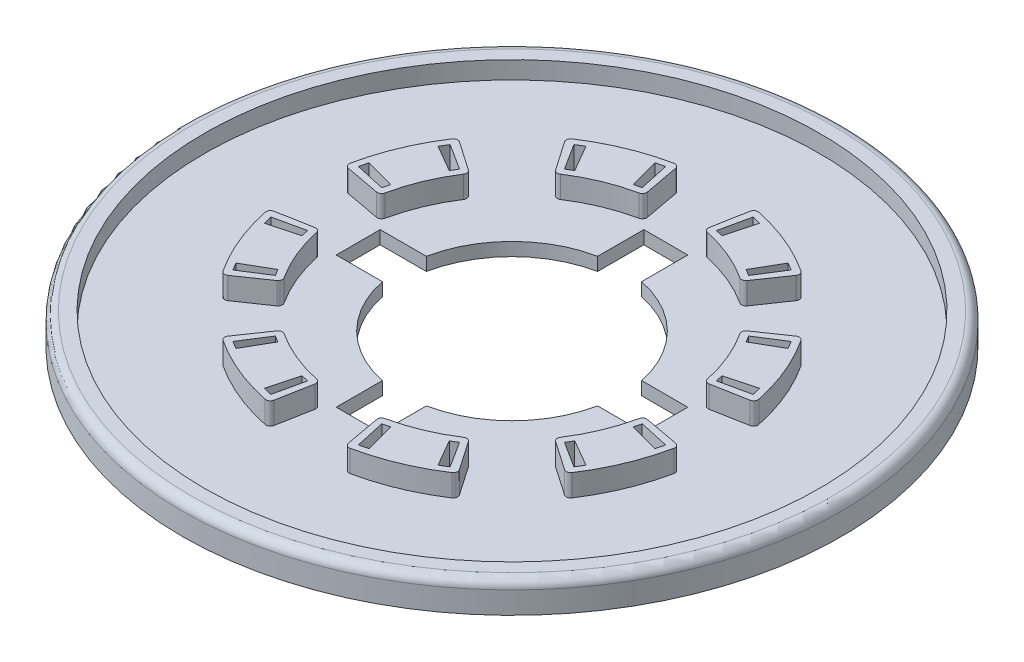
SolidWorks part; units mm, degrees
ref_plane "Alzado" through (0, 0, 0) normal (0, 0, 1) x (1, 0, 0)
ref_plane "Planta" through (0, 0, 0) normal (0, 1, 0) x (1, 0, 0)
ref_plane "Vista lateral" through (0, 0, 0) normal (1, 0, 0) x (0, 0, -1)
sketch "Croquis1" plane through (0, 0, 0) normal (0, 1, 0) x (1, 0, 0)
  circle A0 centre (0, 0) radius 75
  dimension "D1" = 150
extrude "Saliente-Extruir1" add sketch "Croquis1" along normal blind 3
sketch "Croquis3" plane through (0, 3, 0) normal (0, 1, 0) x (1, 0, 0)
  line L0 (-70, 0) -> (70, 0) construction
  line L1 (0, -70) -> (0, 70) construction
  line L3 (-49.4975, -49.4975) -> (49.4975, 49.4975) construction
  line L5 (-49.4975, 49.4975) -> (49.4975, -49.4975) construction
  circle A0 centre (0, 0) radius 75
  circle A1 centre (0, 0) radius 70
  dimension "D1" = 150
  dimension "D2" = 5
extrude "Saliente-Extruir2" add sketch "Croquis3" along normal blind 4
sketch "Croquis7" plane through (0, 3, 0) normal (0, 1, 0) x (1, 0, 0)
  line L0 (51.6188, -52.6795) -> (52.6795, -51.6188)
  line L9 (73.75, -0.75) -> (-73.75, -0.75)
  line L10 (73.75, -0.75) -> (73.75, 0.75)
  line L11 (73.75, 0.75) -> (-73.75, 0.75)
  line L12 (-73.75, -0.75) -> (-73.75, 0.75)
  line L13 (73.75, -0.75) -> (-73.75, 0.75) construction
  line L14 (73.75, 0.75) -> (-73.75, -0.75) construction
  line L15 (51.6188, -52.6795) -> (-52.6795, 51.6188)
  line L16 (-52.6795, 51.6188) -> (-51.6188, 52.6795)
  line L17 (52.6795, -51.6188) -> (-51.6188, 52.6795)
  line L18 (-0.75, -73.75) -> (0.75, -73.75)
  line L19 (-0.75, -73.75) -> (-0.75, 73.75)
  line L20 (-0.75, 73.75) -> (0.75, 73.75)
  line L21 (0.75, -73.75) -> (0.75, 73.75)
  line L22 (-52.6795, -51.6188) -> (-51.6188, -52.6795)
  line L23 (-52.6795, -51.6188) -> (51.6188, 52.6795)
  line L24 (51.6188, 52.6795) -> (52.6795, 51.6188)
  line L25 (-51.6188, -52.6795) -> (52.6795, 51.6188)
  line L26 (-73.75, 0.75) -> (-73.75, -0.75)
  line L27 (-73.75, 0.75) -> (73.75, 0.75)
  line L28 (73.75, 0.75) -> (73.75, -0.75)
  line L29 (-73.75, -0.75) -> (73.75, -0.75)
  point P0 (0, 0)
  point P25 (0, 0)
  dimension "D1" = 1.5
  dimension "D2" = 147.5
  dimension "D3" = 5
sketch "Croquis2" plane through (0, 0, 0) normal (0, -1, 0) x (1, 0, 0)
  line L0 (0, 0) -> (-75, 0) construction
  line L2 (0, 0) -> (-69.291, 28.7013) construction
  circle A0 centre (0, 0) radius 75 construction
  circle A1 centre (-55.4328, 22.961) radius 3.75
  circle A2 centre (-22.961, 55.4328) radius 3.75
  circle A3 centre (22.961, 55.4328) radius 3.75
  circle A4 centre (55.4328, 22.961) radius 3.75
  circle A5 centre (55.4328, -22.961) radius 3.75
  circle A6 centre (22.961, -55.4328) radius 3.75
  circle A7 centre (-22.961, -55.4328) radius 3.75
  circle A8 centre (-55.4328, -22.961) radius 3.75
  point P25 (0, 0)
  dimension "D1" = 7.5
  dimension "D2" = 60
  dimension "D4" = 22.5
  dimension "D3" = 8
extrude "Saliente-Extruir3" [suppressed] add sketch "Croquis7" along normal blind 1 contours L11 L19 L17 L15 | L11 L12 L9 L10 | L21 L20 L19 L18 | L23 L24 L25 L22 | L15 L16 L17 L0
sketch "Croquis4" plane through (0, 0, 0) normal (0, -1, 0) x (1, 0, 0)
  circle A0 centre (0, 0) radius 25
  dimension "D1" = 50
extrude "Cortar-Extruir2" cut sketch "Croquis4" against normal blind 6
sketch "Croquis8" plane through (0, 3, 0) normal (0, 1, 0) x (1, 0, 0)
  line L0 (-45.7108, -8.472) -> (-37.8425, -7.0137)
  line L1 (-38.313, -26.3318) -> (-31.7182, -21.7993)
  line L2 (-38.313, 26.3318) -> (-31.7182, 21.7993)
  line L4 (-45.7108, 8.472) -> (-37.8425, 7.0137)
  line L20 (0, 0) -> (-75, 0) construction
  line L35 (-8.472, 45.7108) -> (-7.0137, 37.8425)
  line L36 (-26.3318, 38.313) -> (-21.7993, 31.7182)
  line L37 (26.3318, 38.313) -> (21.7993, 31.7182)
  line L38 (8.472, 45.7108) -> (7.0137, 37.8425)
  line L39 (45.7108, 8.472) -> (37.8425, 7.0137)
  line L40 (38.313, 26.3318) -> (31.7182, 21.7993)
  line L41 (38.313, -26.3318) -> (31.7182, -21.7993)
  line L42 (45.7108, -8.472) -> (37.8425, -7.0137)
  line L43 (8.472, -45.7108) -> (7.0137, -37.8425)
  line L44 (26.3318, -38.313) -> (21.7993, -31.7182)
  line L45 (-26.3318, -38.313) -> (-21.7993, -31.7182)
  line L46 (-8.472, -45.7108) -> (-7.0137, -37.8425)
  circle A0 centre (0, 0) radius 37.5 construction
  circle A1 centre (0, 0) radius 47.5 construction
  arc A2 (-36.6821, -7.7892) -> (-31.446, -20.4303) centre (0, 0) ccw
  arc A3 (-39.7155, -26.0562) -> (-46.5077, -9.6586) centre (0, 0) cw
  circle A52 centre (0, 0) radius 75 construction
  arc A53 (-38.313, -26.3318) -> (-39.7155, -26.0562) centre (-38.8794, -25.5077) cw
  arc A54 (-31.7182, -21.7993) -> (-31.446, -20.4303) centre (-32.2846, -20.9752) ccw
  arc A55 (-37.8425, -7.0137) -> (-36.6821, -7.7892) centre (-37.6603, -7.997) cw
  arc A56 (-45.7108, -8.472) -> (-46.5077, -9.6586) centre (-45.5285, -9.4552) ccw
  arc A57 (-46.5077, 9.6586) -> (-39.7155, 26.0562) centre (0, 0) cw
  arc A58 (-38.313, 26.3318) -> (-39.7155, 26.0562) centre (-38.8794, 25.5077) ccw
  arc A59 (-45.7108, 8.472) -> (-46.5077, 9.6586) centre (-45.5285, 9.4552) cw
  arc A60 (-31.7182, 21.7993) -> (-31.446, 20.4303) centre (-32.2846, 20.9752) cw
  arc A61 (-31.446, 20.4303) -> (-36.6821, 7.7892) centre (0, 0) ccw
  arc A62 (-37.8425, 7.0137) -> (-36.6821, 7.7892) centre (-37.6603, 7.997) ccw
  arc A63 (-26.0562, 39.7155) -> (-9.6586, 46.5077) centre (0, 0) cw
  arc A64 (-8.472, 45.7108) -> (-9.6586, 46.5077) centre (-9.4552, 45.5285) ccw
  arc A65 (-26.3318, 38.313) -> (-26.0562, 39.7155) centre (-25.5077, 38.8794) cw
  arc A66 (-7.0137, 37.8425) -> (-7.7892, 36.6821) centre (-7.997, 37.6603) cw
  arc A67 (-7.7892, 36.6821) -> (-20.4303, 31.446) centre (0, 0) ccw
  arc A68 (-21.7993, 31.7182) -> (-20.4303, 31.446) centre (-20.9752, 32.2846) ccw
  arc A69 (9.6586, 46.5077) -> (26.0562, 39.7155) centre (0, 0) cw
  arc A70 (26.3318, 38.313) -> (26.0562, 39.7155) centre (25.5077, 38.8794) ccw
  arc A71 (8.472, 45.7108) -> (9.6586, 46.5077) centre (9.4552, 45.5285) cw
  arc A72 (21.7993, 31.7182) -> (20.4303, 31.446) centre (20.9752, 32.2846) cw
  arc A73 (20.4303, 31.446) -> (7.7892, 36.6821) centre (0, 0) ccw
  arc A74 (7.0137, 37.8425) -> (7.7892, 36.6821) centre (7.997, 37.6603) ccw
  arc A75 (39.7155, 26.0562) -> (46.5077, 9.6586) centre (0, 0) cw
  arc A76 (45.7108, 8.472) -> (46.5077, 9.6586) centre (45.5285, 9.4552) ccw
  arc A77 (38.313, 26.3318) -> (39.7155, 26.0562) centre (38.8794, 25.5077) cw
  arc A78 (37.8425, 7.0137) -> (36.6821, 7.7892) centre (37.6603, 7.997) cw
  arc A79 (36.6821, 7.7892) -> (31.446, 20.4303) centre (0, 0) ccw
  arc A80 (31.7182, 21.7993) -> (31.446, 20.4303) centre (32.2846, 20.9752) ccw
  arc A81 (46.5077, -9.6586) -> (39.7155, -26.0562) centre (0, 0) cw
  arc A82 (38.313, -26.3318) -> (39.7155, -26.0562) centre (38.8794, -25.5077) ccw
  arc A83 (45.7108, -8.472) -> (46.5077, -9.6586) centre (45.5285, -9.4552) cw
  arc A84 (31.7182, -21.7993) -> (31.446, -20.4303) centre (32.2846, -20.9752) cw
  arc A85 (31.446, -20.4303) -> (36.6821, -7.7892) centre (0, 0) ccw
  arc A86 (37.8425, -7.0137) -> (36.6821, -7.7892) centre (37.6603, -7.997) ccw
  arc A87 (26.0562, -39.7155) -> (9.6586, -46.5077) centre (0, 0) cw
  arc A88 (8.472, -45.7108) -> (9.6586, -46.5077) centre (9.4552, -45.5285) ccw
  arc A89 (26.3318, -38.313) -> (26.0562, -39.7155) centre (25.5077, -38.8794) cw
  arc A90 (7.0137, -37.8425) -> (7.7892, -36.6821) centre (7.997, -37.6603) cw
  arc A91 (7.7892, -36.6821) -> (20.4303, -31.446) centre (0, 0) ccw
  arc A92 (21.7993, -31.7182) -> (20.4303, -31.446) centre (20.9752, -32.2846) ccw
  arc A93 (-9.6586, -46.5077) -> (-26.0562, -39.7155) centre (0, 0) cw
  arc A94 (-26.3318, -38.313) -> (-26.0562, -39.7155) centre (-25.5077, -38.8794) ccw
  arc A95 (-8.472, -45.7108) -> (-9.6586, -46.5077) centre (-9.4552, -45.5285) cw
  arc A96 (-21.7993, -31.7182) -> (-20.4303, -31.446) centre (-20.9752, -32.2846) cw
  arc A97 (-20.4303, -31.446) -> (-7.7892, -36.6821) centre (0, 0) ccw
  arc A98 (-7.0137, -37.8425) -> (-7.7892, -36.6821) centre (-7.997, -37.6603) ccw
  point P10 (-39.146, -26.9043)
  point P18 (-30.9047, -21.2402)
  point P21 (-36.8721, -6.8338)
  point P24 (-46.7046, -8.6562)
  point P45 (0, 0)
  point P113 (0, 0)
  point P115 (0, 0)
  dimension "D1" = 75
  dimension "D2" = 95
  dimension "D6" = 8
  dimension "D5" = 1
  dimension "D3" = 10.5
  dimension "D4" = 24
extrude "Saliente-Extruir4" add sketch "Croquis8" along normal blind 5
sketch "Croquis10" plane through (0, 8, 0) normal (0, 1, 0) x (1, 0, 0)
  line L0 (-44.9096, -9.9562) -> (-38.0755, -8.4411)
  line L1 (-44.4326, -11.9057) -> (-37.6711, -10.0939)
  line L2 (-37.8425, -7.0137) -> (-45.7108, -8.472) construction
  line L3 (0, 0) -> (-43.8843, -18.1775) construction
  line L34 (-39.8372, 23) -> (-33.775, 19.5)
  line L35 (-38.796, -24.7158) -> (-32.8923, -20.9547)
  line L36 (-39.8372, -23) -> (-33.775, -19.5)
  line L37 (-38.796, 24.7158) -> (-32.8923, 20.9547)
  line L38 (-44.9096, 9.9562) -> (-38.0755, 8.4411)
  line L39 (-44.4326, 11.9057) -> (-37.6711, 10.0939)
  line L40 (-11.9057, 44.4326) -> (-10.0939, 37.6711)
  line L41 (-9.9562, 44.9096) -> (-8.4411, 38.0755)
  line L42 (-24.7158, 38.796) -> (-20.9547, 32.8923)
  line L43 (-23, 39.8372) -> (-19.5, 33.775)
  line L44 (23, 39.8372) -> (19.5, 33.775)
  line L45 (24.7158, 38.796) -> (20.9547, 32.8923)
  line L46 (9.9562, 44.9096) -> (8.4411, 38.0755)
  line L47 (11.9057, 44.4326) -> (10.0939, 37.6711)
  line L48 (44.4326, 11.9057) -> (37.6711, 10.0939)
  line L49 (44.9096, 9.9562) -> (38.0755, 8.4411)
  line L50 (38.796, 24.7158) -> (32.8923, 20.9547)
  line L51 (39.8372, 23) -> (33.775, 19.5)
  line L52 (39.8372, -23) -> (33.775, -19.5)
  line L53 (38.796, -24.7158) -> (32.8923, -20.9547)
  line L54 (44.9096, -9.9562) -> (38.0755, -8.4411)
  line L55 (44.4326, -11.9057) -> (37.6711, -10.0939)
  line L56 (11.9057, -44.4326) -> (10.0939, -37.6711)
  line L57 (9.9562, -44.9096) -> (8.4411, -38.0755)
  line L58 (24.7158, -38.796) -> (20.9547, -32.8923)
  line L59 (23, -39.8372) -> (19.5, -33.775)
  line L60 (-23, -39.8372) -> (-19.5, -33.775)
  line L61 (-24.7158, -38.796) -> (-20.9547, -32.8923)
  line L62 (-9.9562, -44.9096) -> (-8.4411, -38.0755)
  line L63 (-11.9057, -44.4326) -> (-10.0939, -37.6711)
  circle A0 centre (0, 0) radius 39 construction
  circle A1 centre (0, 0) radius 46 construction
  arc A2 (-36.6821, -7.7892) -> (-31.446, -20.4303) centre (0, 0) ccw construction
  arc A3 (-46.5077, -9.6586) -> (-39.7155, -26.0562) centre (0, 0) ccw construction
  arc A4 (-38.0755, -8.4411) -> (-37.6711, -10.0939) centre (0, 0) ccw
  arc A5 (-44.9096, -9.9562) -> (-44.4326, -11.9057) centre (0, 0) ccw
  arc A37 (-32.8923, -20.9547) -> (-33.775, -19.5) centre (0, 0) cw
  arc A38 (-38.796, -24.7158) -> (-39.8372, -23) centre (0, 0) cw
  arc A39 (-38.796, 24.7158) -> (-39.8372, 23) centre (0, 0) ccw
  arc A40 (-32.8923, 20.9547) -> (-33.775, 19.5) centre (0, 0) ccw
  arc A41 (-38.0755, 8.4411) -> (-37.6711, 10.0939) centre (0, 0) cw
  arc A42 (-44.9096, 9.9562) -> (-44.4326, 11.9057) centre (0, 0) cw
  arc A43 (-9.9562, 44.9096) -> (-11.9057, 44.4326) centre (0, 0) ccw
  arc A44 (-8.4411, 38.0755) -> (-10.0939, 37.6711) centre (0, 0) ccw
  arc A45 (-20.9547, 32.8923) -> (-19.5, 33.775) centre (0, 0) cw
  arc A46 (-24.7158, 38.796) -> (-23, 39.8372) centre (0, 0) cw
  arc A47 (24.7158, 38.796) -> (23, 39.8372) centre (0, 0) ccw
  arc A48 (20.9547, 32.8923) -> (19.5, 33.775) centre (0, 0) ccw
  arc A49 (8.4411, 38.0755) -> (10.0939, 37.6711) centre (0, 0) cw
  arc A50 (9.9562, 44.9096) -> (11.9057, 44.4326) centre (0, 0) cw
  arc A51 (44.9096, 9.9562) -> (44.4326, 11.9057) centre (0, 0) ccw
  arc A52 (38.0755, 8.4411) -> (37.6711, 10.0939) centre (0, 0) ccw
  arc A53 (32.8923, 20.9547) -> (33.775, 19.5) centre (0, 0) cw
  arc A54 (38.796, 24.7158) -> (39.8372, 23) centre (0, 0) cw
  arc A55 (38.796, -24.7158) -> (39.8372, -23) centre (0, 0) ccw
  arc A56 (32.8923, -20.9547) -> (33.775, -19.5) centre (0, 0) ccw
  arc A57 (38.0755, -8.4411) -> (37.6711, -10.0939) centre (0, 0) cw
  arc A58 (44.9096, -9.9562) -> (44.4326, -11.9057) centre (0, 0) cw
  arc A59 (9.9562, -44.9096) -> (11.9057, -44.4326) centre (0, 0) ccw
  arc A60 (8.4411, -38.0755) -> (10.0939, -37.6711) centre (0, 0) ccw
  arc A61 (20.9547, -32.8923) -> (19.5, -33.775) centre (0, 0) cw
  arc A62 (24.7158, -38.796) -> (23, -39.8372) centre (0, 0) cw
  arc A63 (-24.7158, -38.796) -> (-23, -39.8372) centre (0, 0) ccw
  arc A64 (-20.9547, -32.8923) -> (-19.5, -33.775) centre (0, 0) ccw
  arc A65 (-8.4411, -38.0755) -> (-10.0939, -37.6711) centre (0, 0) cw
  arc A66 (-9.9562, -44.9096) -> (-11.9057, -44.4326) centre (0, 0) cw
  point P82 (0, 0)
  dimension "D1" = 1.5
  dimension "D2" = 1.5
  dimension "D5" = 8
  dimension "D3" = 2
  dimension "D4" = 2.5
extrude "Cortar-Extruir3" cut sketch "Croquis10" against normal blind 11
fillet "Redondeo1" radius 2 1 edges at (0, 7, 75)
sketch "Croquis11" plane through (0, 3, 0) normal (0, 1, 0) x (1, 0, 0)
  line L0 (-5, -35) -> (5, -35)
  line L1 (35, -5) -> (-35, -5)
  line L2 (35, -5) -> (35, 5)
  line L3 (35, 5) -> (-35, 5)
  line L4 (-35, -5) -> (-35, 5)
  line L5 (35, -5) -> (-35, 5) construction
  line L6 (35, 5) -> (-35, -5) construction
  line L7 (-5, -35) -> (-5, 35)
  line L8 (-5, 35) -> (5, 35)
  line L9 (5, -35) -> (5, 35)
  point P0 (0, 0)
  point P13 (0, 0)
  dimension "D1" = 70
  dimension "D2" = 10
  dimension "D3" = 2
extrude "Cortar-Extruir4" cut sketch "Croquis11" against normal blind 10 contours L4 L1 L3 | L9 L8 L7 | L2 L3 L1 | L0 L9 L7 region at (0, 3, 20) region at (-20, 3, 0) region at (20, 3, 0) region at (0, 3, -20)
extrude "Cortar-Extruir6" cut sketch "Croquis2" against normal blind 2.5
